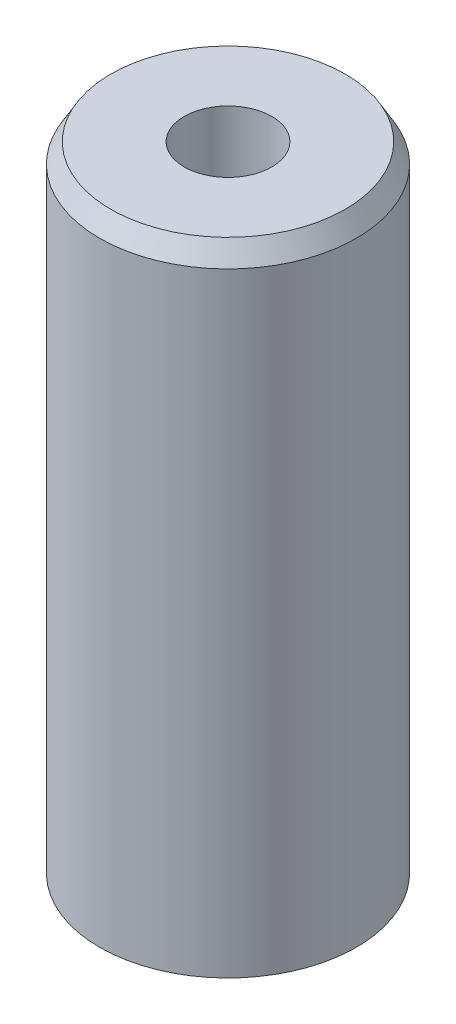
SolidWorks part; units mm, degrees
ref_plane "Front Plane" through (0, 0, 0) normal (0, 0, 1) x (1, 0, 0)
ref_plane "Top Plane" through (0, 0, 0) normal (0, 1, 0) x (1, 0, 0)
ref_plane "Right Plane" through (0, 0, 0) normal (1, 0, 0) x (0, 0, -1)
sketch "Sketch1" plane through (0, 0, 0) normal (0, 1, 0) x (1, 0, 0)
  circle A0 centre (0, 0) radius 35
  dimension "SHAFT_OD" = 70
extrude "Boss-Extrude1" add sketch "Sketch1" along normal blind 175.7237
sketch "Sketch2" plane through (0, 0, 0) normal (0, 1, 0) x (1, 0, 0)
  circle A0 centre (0, 0) radius 11.9396
  dimension "BORE_D" = 23.8792
extrude "Cut-Extrude1" cut sketch "Sketch2" along normal through all
chamfer "Chamfer1" distance 5.2964 angle 30 2 edges at (0, 175.7237, 35) (0, 0, 35) first distance on face at (0, 175.7237, 35) first distance on face at (0, 0, 11.9396)
